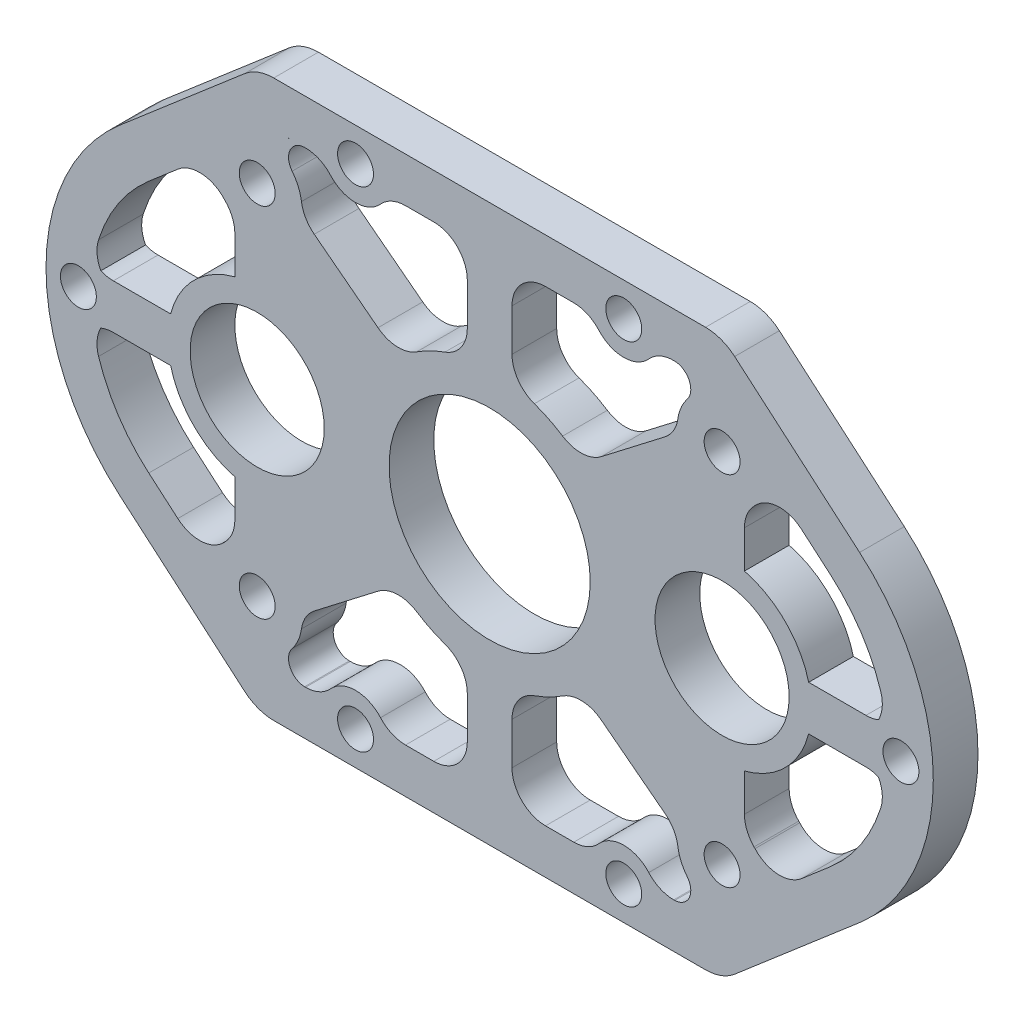
SolidWorks part; units mm, degrees
material "6061-T6 (SS)"
ref_plane "Front Plane" through (0, 0, 0) normal (0, 0, 1) x (1, 0, 0)
ref_plane "Top Plane" through (0, 0, 0) normal (0, 1, 0) x (1, 0, 0)
ref_plane "Right Plane" through (0, 0, 0) normal (1, 0, 0) x (0, 0, -1)
sketch "Sketch1" plane through (0, 0, 0) normal (0, 0, 1) x (1, 0, 0)
  line L0 (127, 25.4) -> (127, 0) construction
  line L1 (0, 0) -> (254, 0)
  line L2 (0, 0) -> (0, 25.4)
  line L3 (0, 25.4) -> (254, 25.4)
  line L4 (254, 0) -> (254, 25.4)
  line L18 (110.6338, 19.05) -> (106.9677, 12.7)
  line L19 (106.9677, 12.7) -> (110.6338, 6.35)
  line L20 (110.6338, 6.35) -> (117.9662, 6.35)
  line L21 (117.9662, 6.35) -> (121.6323, 12.7)
  line L22 (121.6323, 12.7) -> (117.9662, 19.05)
  line L23 (117.9662, 19.05) -> (110.6338, 19.05)
  circle A0 centre (81.28, 12.7) radius 30 construction
  circle A1 centre (147.32, 12.7) radius 30 construction
  circle A2 centre (81.28, 12.7) radius 7.62 construction
  circle A3 centre (147.32, 12.7) radius 8.636
  circle A4 centre (81.28, 12.7) radius 8.636
  circle A5 centre (147.32, 12.7) radius 7.62 construction
  circle A6 centre (114.3, 12.7) radius 25.4 construction
  circle A7 centre (114.3, 12.7) radius 26.67
  circle A8 centre (114.3, 12.7) radius 22.2377 construction
  circle A11 centre (114.3, 12.7) radius 6.35 construction
  point P46 (0, 12.7)
  dimension "D4" = 17.272
  dimension "D9" = 53.34
  dimension "D13" = 12.7
  dimension "D1" = 25.4
  dimension "D2" = 254
  dimension "D10" = 12.7
  dimension "D12" = 12.7
sketch "Sketch3" plane through (0, 0, 0) normal (0, 0, 1) x (1, 0, 0)
  line L0 (81.28, 42.7) -> (147.32, 42.7) construction
  line L5 (81.28, 12.7) -> (114.3, 12.7) construction
  line L6 (114.3, 12.7) -> (147.32, 12.7) construction
  line L9 (114.3, 42.7) -> (114.3, -17.3) construction
  line L10 (61.7477, 35.4704) -> (81.28, 52.225)
  line L25 (81.28, 52.225) -> (147.32, 52.225)
  line L26 (147.32, 52.225) -> (166.8523, 35.4704)
  line L27 (110.6338, 19.05) -> (106.9677, 12.7)
  line L28 (106.9677, 12.7) -> (110.6338, 6.35)
  line L29 (110.6338, 6.35) -> (117.9662, 6.35)
  line L30 (117.9662, 6.35) -> (121.6323, 12.7)
  line L31 (121.6323, 12.7) -> (117.9662, 19.05)
  line L32 (117.9662, 19.05) -> (110.6338, 19.05)
  line L33 (110.565, 18.9308) -> (106.9677, 12.7)
  line L34 (106.9677, 12.7) -> (110.6338, 6.35)
  line L35 (110.6338, 6.35) -> (117.9662, 6.35)
  line L36 (117.9662, 6.35) -> (121.6323, 12.7)
  line L37 (121.6323, 12.7) -> (117.9662, 19.05)
  line L38 (117.9662, 19.05) -> (110.6338, 19.05)
  line L39 (96.3395, 30.6605) -> (132.2605, -5.2605) construction
  line L40 (99.2405, 30.6605) -> (81.28, 12.7) construction
  line L41 (95.25, 47.4625) -> (133.35, 47.4625) construction
  line L42 (81.28, -17.3) -> (147.32, -17.3) construction
  line L43 (95.25, -22.0625) -> (133.35, -22.0625) construction
  line L44 (147.32, -26.825) -> (166.8523, -10.0704)
  line L45 (81.28, -26.825) -> (147.32, -26.825)
  line L46 (61.7477, -10.0704) -> (81.28, -26.825)
  line L47 (81.28, 12.7) -> (81.28, -12.7) construction
  line L48 (81.28, 12.7) -> (81.28, -12.7) construction
  line L49 (81.28, 12.7) -> (55.88, 12.7) construction
  circle A2 centre (81.28, 12.7) radius 30 construction
  circle A9 centre (114.3, 12.7) radius 26.67
  circle A10 centre (114.3, 12.7) radius 26.67 construction
  circle A11 centre (81.28, 12.7) radius 8.636
  circle A12 centre (81.28, 12.7) radius 8.636 construction
  circle A13 centre (147.32, 12.7) radius 8.636
  circle A16 centre (147.32, 12.7) radius 8.636 construction
  circle A17 centre (95.25, 47.4625) radius 2.5527
  circle A19 centre (114.3, 12.7) radius 25.4 construction
  circle A20 centre (114.3, 12.7) radius 22.2377 construction
  circle A22 centre (114.3, 12.7) radius 25.4 construction
  circle A23 centre (114.3, 12.7) radius 22.2377 construction
  arc A24 (108.3271, 25.6791) -> (108.3271, -0.2791) centre (81.28, 12.7) ccw
  circle A25 centre (114.3, 12.7) radius 14.2875
  circle A26 centre (81.28, 12.7) radius 9.525
  circle A27 centre (147.32, 12.7) radius 9.525
  circle A37 centre (133.35, 47.4625) radius 2.5527
  circle A38 centre (133.35, -22.0625) radius 2.5527
  circle A39 centre (95.25, -22.0625) radius 2.5527
  circle A40 centre (81.28, -12.7) radius 2.5527
  circle A41 centre (55.88, 12.7) radius 2.5527
  circle A42 centre (81.28, 38.1) radius 2.5527
  circle A43 centre (147.32, -12.7) radius 2.5527
  circle A44 centre (172.72, 12.7) radius 2.5527
  circle A45 centre (147.32, 38.1) radius 2.5527
  arc A47 (120.2729, -0.2791) -> (120.2729, 25.6791) centre (147.32, 12.7) ccw
  point P1 (0, 0)
  point P2 (114.3, 42.7)
  point P41 (114.3, 52.225)
  point P59 (114.3, 47.4625)
  point P69 (114.3, 12.7)
  point P78 (81.28, 12.7)
  point P84 (114.3, -22.0625)
  dimension "D3" = 45
  dimension "D4" = 9.525
  dimension "D2" = 45
  dimension "D8" = 25.4
  dimension "D14" = 28.575
  dimension "D15" = 19.05
  dimension "D16" = 3
  dimension "D5" = 5.1054
  dimension "D12" = 5.1054
  dimension "D7" = 4.7625
  dimension "D17" = 90
  dimension "2" = 50.8
  dimension "D6" = 19.05
  dimension "D9" = 0
  dimension "D10" = 0
  dimension "D11" = 0
  dimension "D13" = 0
extrude "Boss-Extrude1" add sketch "Sketch3" along normal blind 6.35 contours A24 A10 L26 L25 L10 A37 A17 | A24 L46 L45 L44 A10 A38 A39 | A10 A24 A12 A40 A42 | A23 A24 A25 | A23 A22 A12 | A22 A24 A10 A12 | A22 A12 A10 A24 | A24 A22 A23 | A24 A10 A22 | A22 A24 A23 | A25 A24 A23 | A25 A23 A24 | A24 A23 A22 | A24 A22 A10 | A23 A24 A22 | A23 A45 A25 A44 | A22 A45 A23 A44 A16 | A23 A45 A22 | A22 A45 A16 A10 | A10 A16 A43 | A22 A44 A23 | A22 A44 A10 A16 | A10 A26 A12 | A22 A12 A10 | A12 A22 | A10 A27 A16 | A16 A22 | A22 A16 A10 region at (81.1746, 41.9228, 0) region at (114.3, 45.5045, 0) region at (114.3, -20.1045, 0) region at (97.63, 12.7, 0) region at (114.3, 33.2042, 0) region at (114.3, -7.8042, 0) region at (147.4254, 41.9228, 0) region at (130.97, 12.7, 0)
fillet "Fillet2" radius 6.35 4 edges at (147.32, -26.825, 3.175) (81.28, -26.825, 3.175) (147.32, 52.225, 3.175) (81.28, 52.225, 3.175)
sketch "Sketch9" plane through (0, 0, 6.35) normal (0, 0, 1) x (1, 0, 0)
  line L0 (144.9696, -20.475) -> (162.7179, -5.2507)
  line L1 (162.7179, 30.6507) -> (144.9696, 45.875)
  line L2 (144.9696, 45.875) -> (83.6304, 45.875)
  line L3 (83.6304, 45.875) -> (65.8821, 30.6507)
  line L4 (65.8821, -5.2507) -> (83.6304, -20.475)
  line L5 (83.6304, -20.475) -> (144.9696, -20.475)
  line L6 (149.104, -25.2947) -> (166.8523, -10.0704)
  line L7 (166.8523, 35.4704) -> (149.104, 50.6947)
  line L8 (144.9696, 52.225) -> (83.6304, 52.225)
  line L9 (79.496, 50.6947) -> (61.7477, 35.4704)
  line L10 (61.7477, -10.0704) -> (79.496, -25.2947)
  line L11 (83.6304, -26.825) -> (144.9696, -26.825)
  line L12 (149.104, -25.2947) -> (166.8523, -10.0704)
  line L13 (166.8523, 35.4704) -> (149.104, 50.6947)
  line L14 (144.9696, 52.225) -> (83.6304, 52.225)
  line L15 (79.496, 50.6947) -> (61.7477, 35.4704)
  line L16 (61.7477, -10.0704) -> (79.496, -25.2947)
  line L17 (83.6304, -26.825) -> (144.9696, -26.825)
  line L18 (81.28, 38.1) -> (81.28, 12.7) construction
  line L19 (81.28, 12.7) -> (81.28, -12.7) construction
  line L20 (147.32, -12.7) -> (147.32, 12.7) construction
  line L21 (147.32, 12.7) -> (147.32, 38.1) construction
  line L22 (81.28, 12.7) -> (114.3, 12.7) construction
  line L23 (114.3, 12.7) -> (147.32, 12.7) construction
  line L24 (147.32, 12.7) -> (114.3, 12.7) construction
  line L25 (114.3, 12.7) -> (147.32, -12.7) construction
  line L26 (81.28, -12.7) -> (114.3, 12.7) construction
  line L27 (114.3, 12.7) -> (81.28, 38.1) construction
  line L28 (114.3, 12.7) -> (147.32, 38.1) construction
  line L29 (114.3, 12.7) -> (114.3, 45.875) construction
  line L30 (114.3, 12.7) -> (114.3, -20.475) construction
  line L31 (116.2358, 15.2166) -> (83.2158, 40.6166)
  line L32 (112.3642, 10.1834) -> (145.3842, -15.2166)
  line L33 (116.2358, 10.1834) -> (149.2558, 35.5834)
  line L34 (112.3642, 10.1834) -> (79.3442, 35.5834)
  line L35 (116.2358, 15.2166) -> (149.2558, -10.1834)
  line L36 (112.3642, 15.2166) -> (145.3842, 40.6166)
  line L37 (81.28, 12.7) -> (55.88, 12.7) construction
  line L38 (147.32, 12.7) -> (172.72, 12.7) construction
  line L39 (81.28, 9.525) -> (55.88, 9.525)
  line L40 (81.28, 9.525) -> (114.3, 9.525)
  line L41 (114.3, 9.525) -> (147.32, 9.525)
  line L42 (147.32, 9.525) -> (172.72, 9.525)
  line L43 (81.28, 15.875) -> (55.88, 15.875)
  line L44 (81.28, 15.875) -> (114.3, 15.875)
  line L45 (114.3, 15.875) -> (147.32, 15.875)
  line L46 (147.32, 15.875) -> (172.72, 15.875)
  line L47 (83.2158, -15.2166) -> (116.2358, 10.1834)
  line L48 (79.3442, -10.1834) -> (112.3642, 15.2166)
  line L49 (111.125, 12.7) -> (111.125, -20.475)
  line L50 (117.475, 12.7) -> (117.475, -20.475)
  line L51 (117.475, 12.7) -> (117.475, 45.875)
  line L52 (111.125, 12.7) -> (111.125, 45.875)
  line L53 (78.105, 38.1) -> (78.105, 12.7)
  line L54 (78.105, 12.7) -> (78.105, -12.7)
  line L55 (150.495, -12.7) -> (150.495, 12.7)
  line L56 (150.495, 12.7) -> (150.495, 38.1)
  line L57 (84.455, 38.1) -> (84.455, 12.7)
  line L58 (84.455, 12.7) -> (84.455, -12.7)
  line L59 (144.145, -12.7) -> (144.145, 12.7)
  line L60 (144.145, 12.7) -> (144.145, 38.1)
  circle A0 centre (55.88, 12.7) radius 4.6
  circle A1 centre (95.25, 47.4625) radius 4.7625
  arc A2 (166.8523, -10.0704) -> (166.8523, 35.4704) centre (147.32, 12.7) ccw
  arc A3 (61.7477, 35.4704) -> (61.7477, -10.0704) centre (81.28, 12.7) ccw
  arc A4 (166.8523, -10.0704) -> (166.8523, 35.4704) centre (147.32, 12.7) ccw
  arc A5 (61.7477, 35.4704) -> (61.7477, -10.0704) centre (81.28, 12.7) ccw
  circle A6 centre (133.35, 47.4625) radius 4.7625
  circle A7 centre (172.72, 12.7) radius 4.6
  circle A8 centre (133.35, -22.0625) radius 4.7625
  circle A9 centre (95.25, -22.0625) radius 4.7625
  circle A10 centre (81.28, 12.7) radius 9.525
  circle A11 centre (81.28, -12.7) radius 6.35
  circle A12 centre (81.28, 38.1) radius 6.35
  circle A13 centre (147.32, 38.1) radius 6.35
  circle A14 centre (147.32, 12.7) radius 9.525
  circle A15 centre (147.32, -12.7) radius 6.35
  arc A16 (144.9696, -26.825) -> (149.104, -25.2947) centre (144.9696, -20.475) ccw
  arc A17 (144.9696, -26.825) -> (149.104, -25.2947) centre (144.9696, -20.475) ccw
  arc A18 (149.104, 50.6947) -> (144.9696, 52.225) centre (144.9696, 45.875) ccw
  arc A19 (149.104, 50.6947) -> (144.9696, 52.225) centre (144.9696, 45.875) ccw
  arc A20 (83.6304, 52.225) -> (79.496, 50.6947) centre (83.6304, 45.875) ccw
  arc A21 (83.6304, 52.225) -> (79.496, 50.6947) centre (83.6304, 45.875) ccw
  arc A22 (79.496, -25.2947) -> (83.6304, -26.825) centre (83.6304, -20.475) ccw
  arc A23 (79.496, -25.2947) -> (83.6304, -26.825) centre (83.6304, -20.475) ccw
  arc A24 (162.7179, -5.2507) -> (162.7179, 30.6507) centre (147.32, 12.7) ccw
  arc A25 (144.9696, 45.875) -> (144.9696, 45.875) centre (144.9696, 45.875) ccw
  arc A26 (83.6304, 45.875) -> (83.6304, 45.875) centre (83.6304, 45.875) ccw
  arc A27 (65.8821, 30.6507) -> (65.8821, -5.2507) centre (81.28, 12.7) ccw
  arc A28 (83.6304, -20.475) -> (83.6304, -20.475) centre (83.6304, -20.475) ccw
  arc A29 (144.9696, -20.475) -> (144.9696, -20.475) centre (144.9696, -20.475) ccw
  circle A30 centre (114.3, 12.7) radius 19.05
  circle A32 centre (81.28, 12.7) radius 12.7
  circle A33 centre (147.32, 12.7) radius 12.7
  dimension "D2" = 19.05
  dimension "D3" = 12.7
  dimension "D4" = 38.1
  dimension "D18" = 25.4
  dimension "D17" = 6.35
  dimension "D1" = 0
  dimension "D5" = 3.175
  dimension "D6" = 3.175
  dimension "D7" = 3.175
  dimension "D8" = 3.175
  dimension "D9" = 3.175
  dimension "D10" = 3.175
  dimension "D11" = 3.175
  dimension "D12" = 3.175
  dimension "D13" = 3.175
  dimension "D14" = 3.175
  dimension "D15" = 3.175
  dimension "D16" = 3.175
extrude "Cut-Extrude2" cut sketch "Sketch9" against normal blind 6.35 contours A32 L53 A12 L3 A27 A0 L43 | A32 L39 A0 A27 L4 A11 L54 | A30 L52 L2 A1 L3 A12 L31 | A30 L36 A13 L1 L2 A6 L51 | A33 L46 A7 A24 L1 A13 L56 | A33 L55 A15 L0 A24 A7 L42 | A30 L50 L5 A8 L0 A15 L32 | A30 L47 A11 L4 L5 A9 L49 region at (128.7733, -12.6609, 6.35) region at (159.8487, -0.042, 6.35) region at (99.8267, -12.6609, 6.35) region at (159.8487, 25.442, 6.35) region at (68.7513, -0.042, 6.35) region at (128.7733, 38.0609, 6.35) region at (68.7513, 25.442, 6.35) region at (99.8267, 38.0609, 6.35)
fillet "Fillet3" radius 4.7625 48 edges at (117.475, 45.875, 3.175) (128.8599, 45.875, 3.175) (137.8401, 45.875, 3.175) (144.9696, 45.875, 3.175) (146.6698, 44.4166, 3.175) (141.0253, 37.2636, 3.175) (127.2525, 26.6691, 3.175) (117.475, 31.4836, 3.175) (101.3475, 26.6691, 3.175) (81.9302, 44.4166, 3.175) (83.6304, 45.875, 3.175) (90.7599, 45.875, 3.175) (99.7401, 45.875, 3.175) (111.125, 45.875, 3.175) (111.125, 31.4836, 3.175) (87.5747, 37.2636, 3.175) (111.125, -6.0836, 3.175) (111.125, -20.475, 3.175) (99.7401, -20.475, 3.175) (90.7599, -20.475, 3.175) (81.9302, -19.0166, 3.175) (87.5747, -11.8636, 3.175) (101.3475, -1.2691, 3.175) (83.6304, -20.475, 3.175) (127.2525, -1.2691, 3.175) (141.0253, -11.8636, 3.175) (146.6698, -19.0166, 3.175) (144.9696, -20.475, 3.175) (137.8401, -20.475, 3.175) (128.8599, -20.475, 3.175) (117.475, -6.0836, 3.175) (117.475, -20.475, 3.175) (169.3914, 15.875, 3.175) (150.495, 32.6007, 3.175) (153.662, 38.4188, 3.175) (170.6137, 16.7895, 3.175) (78.105, 32.6007, 3.175) (59.2086, 15.875, 3.175) (74.938, 38.4188, 3.175) (57.9863, 16.7895, 3.175) (78.105, -7.2007, 3.175) (74.938, -13.0188, 3.175) (57.9863, 8.6105, 3.175) (59.2086, 9.525, 3.175) (150.495, -7.2007, 3.175) (153.662, -13.0188, 3.175) (169.3914, 9.525, 3.175) (170.6137, 8.6105, 3.175)
sketch "Sketch11" plane through (0, 0, 6.35) normal (0, 0, 1) x (1, 0, 0)
  line L4 (53.3273, 12.7) -> (175.2727, 12.7) construction
  line L5 (114.3, 52.225) -> (114.3, -26.825) construction
  line L6 (83.6304, 52.225) -> (144.9696, 52.225) construction
  line L7 (83.6304, -26.825) -> (144.9696, -26.825) construction
  line L16 (143.3237, -20.4736) -> (140.4495, -20.475)
  line L17 (143.3237, 45.8736) -> (140.4495, 45.875)
  line L18 (85.2763, 45.8736) -> (88.1505, 45.875)
  line L19 (85.3931, -20.475) -> (88.1505, -20.475) construction
  line L20 (85.3931, -20.475) -> (88.1505, -20.475)
  circle A1 centre (55.88, 12.7) radius 2.5527 construction
  circle A3 centre (172.72, 12.7) radius 2.5527 construction
  arc A17 (86.2424, -16.662) -> (88.1505, -20.475) centre (88.0778, -18.1274) ccw
  arc A18 (86.2424, -16.662) -> (87.568, -13.5855) centre (81.28, -12.7) ccw construction
  arc A19 (86.2424, -16.662) -> (85.2763, -20.4736) centre (89.9642, -19.6335) ccw construction
  arc A21 (142.3576, -16.662) -> (143.3237, -20.4736) centre (138.6358, -19.6335) cw
  arc A22 (142.3576, -16.662) -> (140.4495, -20.475) centre (140.5222, -18.1274) cw
  arc A23 (142.3576, 42.062) -> (140.4495, 45.875) centre (140.5222, 43.5274) ccw
  arc A24 (142.3576, 42.062) -> (143.3237, 45.8736) centre (138.6358, 45.0335) ccw
  arc A25 (86.2424, 42.062) -> (85.2763, 45.8736) centre (89.9642, 45.0335) cw
  arc A26 (86.2424, 42.062) -> (88.1505, 45.875) centre (88.0778, 43.5274) cw
  arc A27 (85.2763, -20.4736) -> (85.3931, -20.475) centre (85.3931, -15.7125) ccw construction
  arc A28 (85.2763, -20.4736) -> (85.3931, -20.475) centre (85.3931, -15.7125) ccw
  arc A29 (86.2424, -16.662) -> (85.2763, -20.4736) centre (89.9642, -19.6335) ccw
extrude "Boss-Extrude3" add sketch "Sketch11" against normal up to surface (6.35 mm away) contours A17 A29 A28 L20 | A21 A22 L16 | A25 A26 L18 | A23 A24 L17 | L17 A23 A24 region at (142.7262, -19.5499, 6.35) region at (142.7262, 44.9499, 6.35) region at (85.8738, 44.9499, 6.35) region at (85.8741, -19.5506, 6.35) up to face at (96.993, 39.8725, 0)
equation "\"NEO\"= 60mm"
equation "\"D3@Sketch1\"=\"NEO\""
equation "\"D5@Sketch1\"=\"NEO\""
